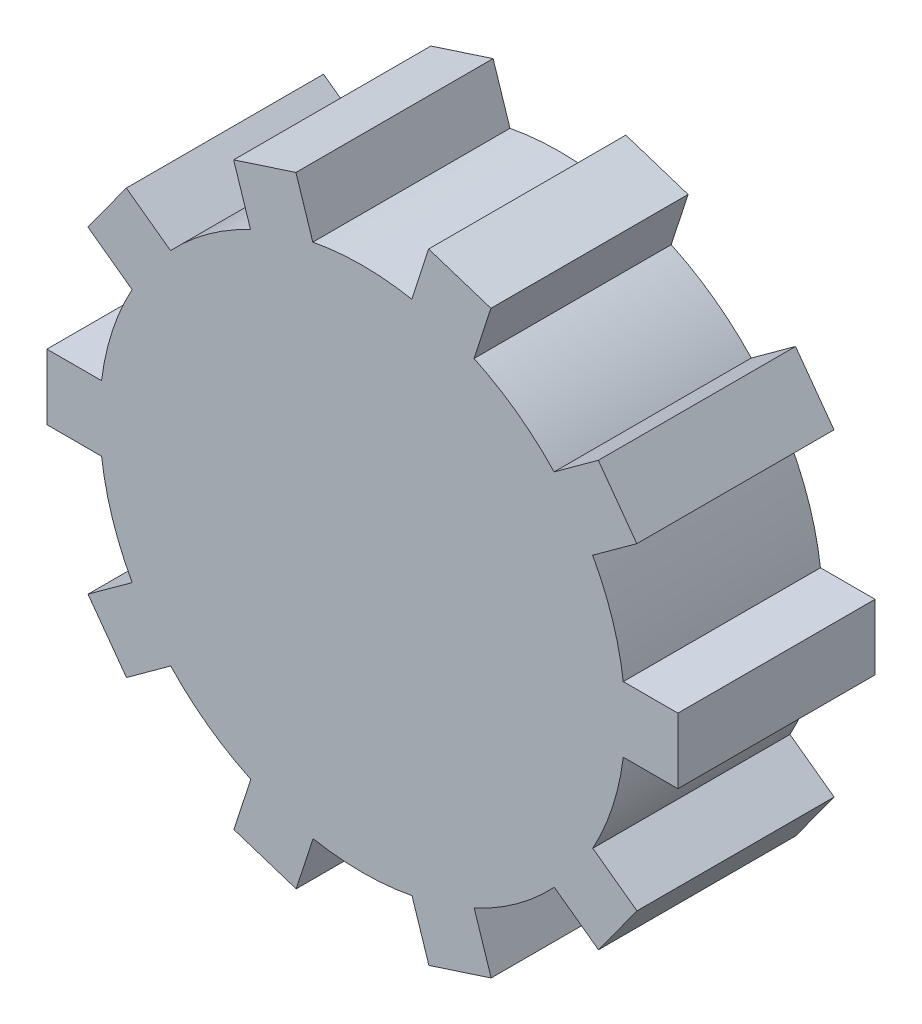
SolidWorks part; units mm, degrees
ref_plane "前视基准面" through (0, 0, 0) normal (0, 0, 1) x (1, 0, 0)
ref_plane "上视基准面" through (0, 0, 0) normal (0, 1, 0) x (1, 0, 0)
ref_plane "右视基准面" through (0, 0, 0) normal (1, 0, 0) x (0, 0, -1)
other "Configuration Table"
sketch "草图1" plane through (0, 0, 0) normal (0, 0, 1) x (1, 0, 0)
  circle A0 centre (0, 0) radius 20
extrude "凸台-拉伸1" add sketch "草图1" along normal blind 15
sketch "草图2" plane through (0, 0, 0) normal (0, 0, 1) x (1, 0, 0)
  line L1 (19.8456, -2.4807) -> (24, -2.4807)
  line L2 (19.8456, -2.4807) -> (19.8456, 2.5)
  line L3 (19.8456, 2.5) -> (24, 2.5)
  line L4 (24, -2.4807) -> (24, 2.5)
  circle A0 centre (0, 0) radius 20 construction
extrude "凸台-拉伸2" add sketch "草图2" along normal blind 15
ref_axis "基准轴1" through (0, 0, 15) along (0, 0, -1)
pattern_circular "阵列(圆周)1" count 10 over 360 about axis through (0, 0, 15) along (0, 0, -1) of "凸台-拉伸2"
